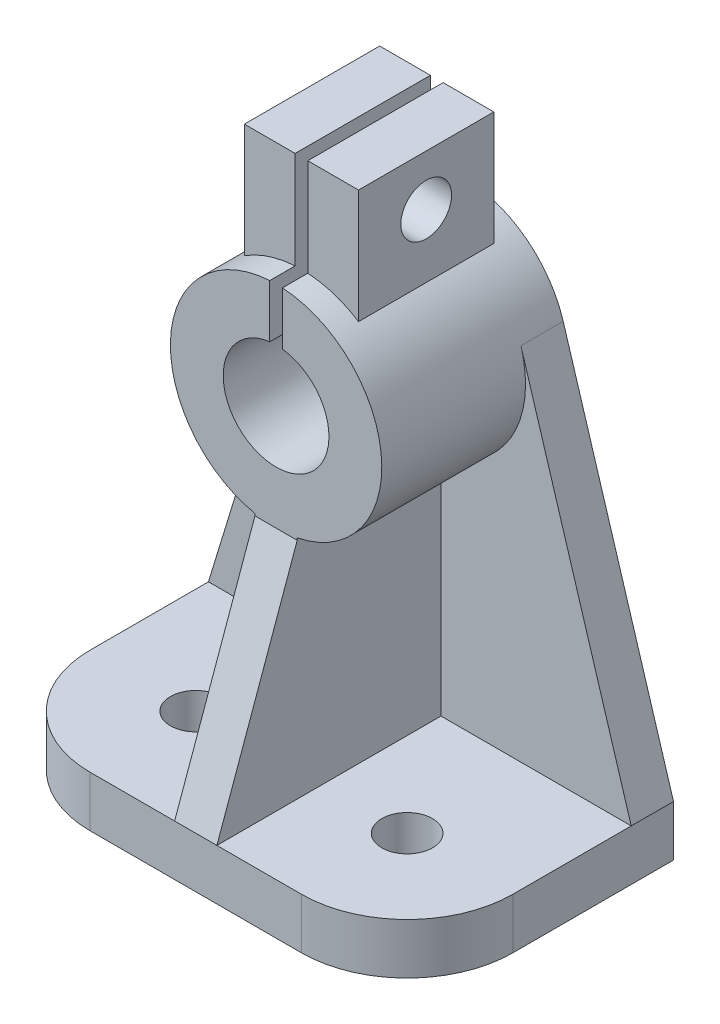
SolidWorks part; units mm, degrees
ref_plane "Front Plane" through (0, 0, 0) normal (0, 0, 1) x (1, 0, 0)
ref_plane "Top Plane" through (0, 0, 0) normal (0, 1, 0) x (1, 0, 0)
ref_plane "Right Plane" through (0, 0, 0) normal (1, 0, 0) x (0, 0, -1)
sketch "Sketch3" plane through (0, 0, 0) normal (0, 1, 0) x (1, 0, 0)
  line L1 (-50, 31.5) -> (50, 31.5)
  line L2 (-50, 31.5) -> (-50, -31.5)
  line L3 (-50, -31.5) -> (50, -31.5)
  line L4 (50, 31.5) -> (50, -31.5)
  line L5 (-50, 31.5) -> (50, -31.5) construction
  line L6 (-50, -31.5) -> (50, 31.5) construction
  point P0 (0, 0)
  dimension "D1" = 100
  dimension "D2" = 63
extrude "Boss-Extrude2" add sketch "Sketch3" along normal blind 12
fillet "Fillet1" radius 25 2 edges at (50, 6, 31.5) (-50, 6, 31.5)
sketch "Sketch4" plane through (0, 12, 0) normal (0, 1, 0) x (1, 0, 0)
  circle A0 centre (-25, -6.5) radius 6
  circle A1 centre (25, -6.5) radius 6
  dimension "D1" = 12
extrude "Cut-Extrude1" cut sketch "Sketch4" against normal through all
sketch "Sketch5" plane through (0, 0, -31.5) normal (0, 0, -1) x (-1, 0, 0)
  line L0 (0, 0) -> (0, 90) construction
  line L1 (-50, 12) -> (-23.9068, 97.312)
  line L2 (50, 12) -> (23.9068, 97.312)
  circle A0 centre (0, 90) radius 25
  line M6 (50, 12) -> (-50, 12)
  dimension "D2" = 50
  dimension "D1" = 90
extrude "Boss-Extrude3" add sketch "Sketch5" against normal blind 10 contours L0 A0 L1 M6 | L0 L2 A0 M6 | A0 region at (21.4549, 40.5565, -31.5) region at (-21.4549, 40.5565, -31.5) region at (19.5288, 75.5512, -31.5)
extrude "Boss-Extrude4" add sketch "Sketch5<3>" against normal blind 44 contours A0 region at (0, 90, -31.5)
sketch "Sketch5<3>" plane through (0, 0, -31.5) normal (0, 0, -1) x (-1, 0, 0) same geometry as "Sketch5"
sketch "Sketch6" plane through (0, 0, 12.5) normal (0, 0, 1) x (1, 0, 0)
  circle A0 centre (0, 90) radius 12.5
  dimension "D1" = 25
extrude "Cut-Extrude2" cut sketch "Sketch6" against normal through all
ref_plane "Plane2" [suppressed] through (0, 138, 0) normal (0, 1, 0) x (1, 0, 0)
sketch "Sketch12" plane through (0, 138, 0) normal (0, 1, 0) x (1, 0, 0)
  line L0 (0, 0) -> (0, 31.5) construction
  line L1 (23.9068, 31.5) -> (-23.9068, 31.5) construction
  line L3 (-13.5, -6.5) -> (13.5, -6.5)
  line L4 (-13.5, -6.5) -> (-13.5, 25.5)
  line L5 (-13.5, 25.5) -> (13.5, 25.5)
  line L6 (13.5, -6.5) -> (13.5, 25.5)
  line L7 (-13.5, -6.5) -> (13.5, 25.5) construction
  line L8 (-13.5, 25.5) -> (13.5, -6.5) construction
  point P5 (0, 9.5)
  dimension "D1" = 27
  dimension "D2" = 32
  dimension "D3" = 6
extrude "Boss-Extrude5" add sketch "Sketch12" against normal up to surface (26.9584 mm away) up to face at (0, 93.656, -26.5)
sketch "Sketch13" plane through (0, 0, 12.5) normal (0, 0, 1) x (1, 0, 0)
  line L0 (0, 90) -> (0, 149.062) construction
  line L2 (-1.5, 82.031) -> (1.5, 82.031)
  line L3 (-1.5, 82.031) -> (-1.5, 157.031)
  line L4 (-1.5, 157.031) -> (1.5, 157.031)
  line L5 (1.5, 82.031) -> (1.5, 157.031)
  line L6 (-1.5, 82.031) -> (1.5, 157.031) construction
  line L7 (-1.5, 157.031) -> (1.5, 82.031) construction
  point P4 (0, 119.531)
  dimension "D1" = 3
  dimension "D2" = 75
extrude "Cut-Extrude3" cut sketch "Sketch13" against normal blind 44
sketch "Sketch16" plane through (13.5, 0, 0) normal (1, 0, 0) x (0, 0, -1)
  line L0 (9.5, 111.0416) -> (9.5, 138) construction
  line L1 (25.5, 111.0416) -> (-6.5, 111.0416) construction
  line L2 (-6.5, 138) -> (25.5, 138) construction
  circle A0 centre (9.5, 126) radius 6
  dimension "D1" = 12
  dimension "D2" = 12
extrude "Cut-Extrude4" cut sketch "Sketch16" against normal through all
sketch "Sketch19" plane through (0, 0, 0) normal (1, 0, 0) x (0, 0, -1)
  line L0 (-31.5, 12) -> (21.5, 12)
  line L1 (21.5, 12) -> (21.5, 65)
  line L2 (21.5, 65) -> (-12.5, 65)
  line L3 (-12.5, 65) -> (-31.5, 12)
extrude "Boss-Extrude14" add sketch "Sketch19" along normal mid plane 10 separate body
sketch "Sketch20" plane through (0, 65, 0) normal (0, 1, 0) x (1, 0, 0)
  line L4 (-5, 21.5) -> (-5, -12.5)
  line L5 (-5, -12.5) -> (5, -12.5)
  line L6 (5, -12.5) -> (5, 21.5)
  line L7 (5, 21.5) -> (-5, 21.5)
  line L8 (-5, 21.5) -> (-5, -12.5)
  line L9 (-5, -12.5) -> (5, -12.5)
  line L10 (5, -12.5) -> (5, 21.5)
  line L11 (5, 21.5) -> (-5, 21.5)
  dimension "D1" = 0
extrude "Boss-Extrude15" add sketch "Sketch20" along normal up to surface up to face at (0, 105.0552, -13.75)
